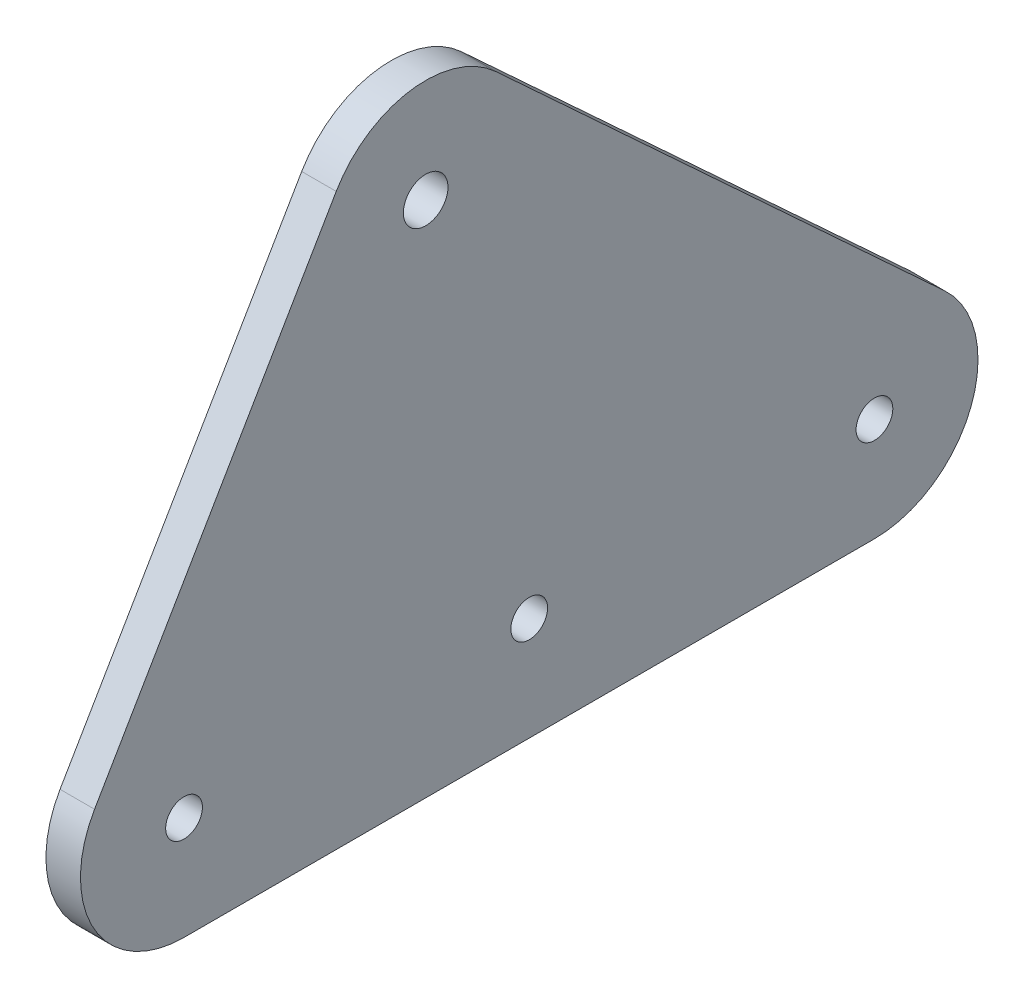
SolidWorks part; units mm, degrees
ref_plane "Front Plane" through (0, 0, 0) normal (0, 0, 1) x (1, 0, 0)
ref_plane "Top Plane" through (0, 0, 0) normal (0, 1, 0) x (1, 0, 0)
ref_plane "Right Plane" through (0, 0, 0) normal (1, 0, 0) x (0, 0, -1)
sketch "Sketch1" plane through (0, 0, 0) normal (1, 0, 0) x (0, 0, -1)
  line L0 (-60.905, -66.6013) -> (-16.455, 9.5987)
  line L1 (12.9212, 13.998) -> (95.4712, -62.202)
  line L2 (-44.45, -95.25) -> (82.55, -95.25)
  arc A0 (12.9212, 13.998) -> (-16.455, 9.5987) centre (0, 0) ccw
  arc A1 (82.55, -95.25) -> (95.4712, -62.202) centre (82.55, -76.2) ccw
  arc A2 (-60.905, -66.6013) -> (-44.45, -95.25) centre (-44.45, -76.2) ccw
  point P14 (0, 0)
  dimension "D1" = 127
  dimension "D2" = 76.2
  dimension "D3" = 44.45
  dimension "D4" = 38.1
extrude "Boss-Extrude1" add sketch "Sketch1" along normal blind 6.35 contours L1 A1 L2 A2 L0 A0
sketch "Sketch2" plane through (6.35, 0, 0) normal (1, 0, 0) x (0, 0, -1)
  line L0 (-44.45, -95.25) -> (82.55, -95.25) construction
  circle A0 centre (-44.45, -76.2) radius 3.3782
  circle A1 centre (19.05, -76.2) radius 3.3782
  circle A2 centre (82.55, -76.2) radius 3.3782
  arc A3 (-60.905, -66.6013) -> (-44.45, -95.25) centre (-44.45, -76.2) ccw construction
  arc A4 (82.55, -95.25) -> (95.4712, -62.202) centre (82.55, -76.2) ccw construction
  circle A5 centre (0, 0) radius 4.1021
  dimension "D2" = 0
  dimension "D3" = 0
  dimension "D4" = 63.5
  dimension "D5" = 6.7564
  dimension "D6" = 8.2042
  dimension "D1" = 19.05
extrude "Cut-Extrude1" cut sketch "Sketch2" against normal up to next
